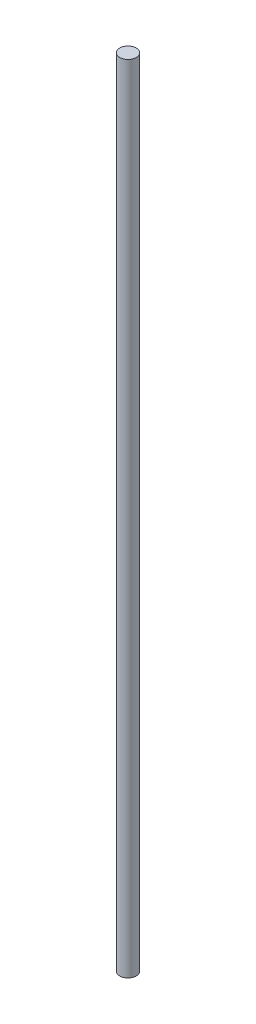
SolidWorks part; units mm, degrees
ref_plane "Front Plane" through (0, 0, 0) normal (0, 0, 1) x (1, 0, 0)
ref_plane "Top Plane" through (0, 0, 0) normal (0, 1, 0) x (1, 0, 0)
ref_plane "Right Plane" through (0, 0, 0) normal (1, 0, 0) x (0, 0, -1)
sketch "Sketch1" plane through (0, 0, 0) normal (0, 1, 0) x (1, 0, 0)
  circle A0 centre (0, 0) radius 4
  dimension "D1" = 8
extrude "Boss-Extrude1" add sketch "Sketch1" along normal blind 385.75
equation "\"d\"= 8"
equation "\"l\"= 385.75"
equation "\"D1@Boss-Extrude1\"=\"l\""
equation "\"D1@Sketch1\"=\"d\""
